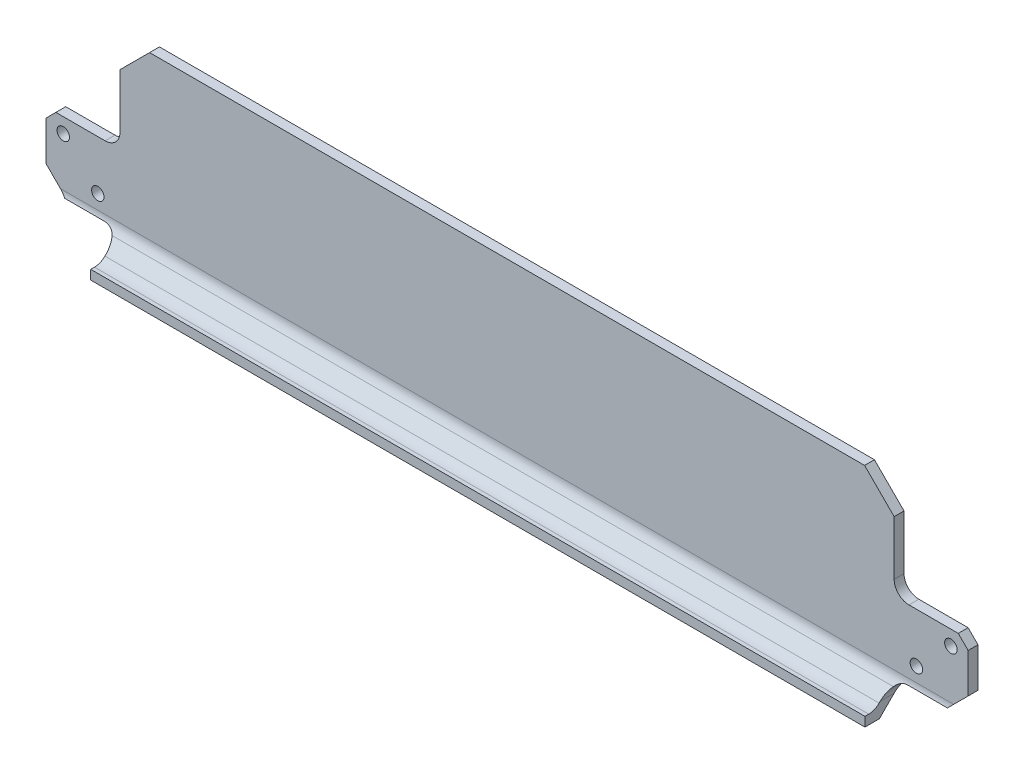
SolidWorks part; units mm, degrees
material "PLA"
ref_plane "Front Plane" through (0, 0, 0) normal (0, 0, 1) x (1, 0, 0)
ref_plane "Top Plane" through (0, 0, 0) normal (0, 1, 0) x (1, 0, 0)
ref_plane "Right Plane" through (0, 0, 0) normal (1, 0, 0) x (0, 0, -1)
sketch "Profile-Sketch" plane through (0, 0, 0) normal (0, 0, 1) x (1, 0, 0)
  line L0 (0, 0) -> (26895.2177, 0) construction
  line L1 (0, 0) -> (0, 26895.2177) construction
  line L2 (-114.3, 12.7) -> (-105.41, 12.7) construction
  line L3 (-114.3, 12.7) -> (-114.3, 21.59) construction
  circle A0 centre (-114.3, 12.7) radius 4 construction
  circle A1 centre (-105.41, 12.7) radius 1.6002 construction
  circle A2 centre (-114.3, 21.59) radius 1.6002 construction
  dimension "D3" = 8
  dimension "D4" = 3.2004
  dimension "D5" = 3.2004
  dimension "D1" = 12.7
  dimension "D2" = 114.3
  dimension "D6" = 8.89
  dimension "D7" = 8.89
sketch "Sketch2" plane through (0, 0, 0) normal (1, 0, 0) x (0, 0, -1)
  line L0 (0, 0) -> (50000, 0) construction
  line L1 (-10.0691, 0) -> (-6.35, 0)
  line L2 (-6.35, 0) -> (0, 6.35)
  line L3 (0, -200000) -> (0, 226895.2177) construction
  line L4 (0, 6.35) -> (0, 50.8)
  line L5 (0, 16.7) -> (0, 8.7) construction
  line L6 (0, 50.8) -> (-2.54, 50.8)
  line L7 (-2.54, 50.8) -> (-2.54, 7.4021)
  line L8 (-2.54, 7.4021) -> (-7.5291, 2.413)
  line L9 (-7.5291, 2.413) -> (-10.0691, 2.413)
  line L10 (-10.0691, 2.413) -> (-10.0691, 0)
  dimension "D1" = 2.54
  dimension "D2" = 50.8
  dimension "D3" = 2.54
  dimension "D4" = 2.413
  dimension "D5" = 45
  dimension "D6" = 2.54
  dimension "D7" = 6.35
extrude "Boss-Extrude1" add sketch "Sketch2" along normal mid plane 199.39
sketch "Sketch3" plane through (0, 0, 0) normal (0, 0, 1) x (1, 0, 0)
  line L0 (-99.695, 25.4) -> (-118.745, 25.4)
  line L1 (-99.695, 50.8) -> (-99.695, 7.4021) construction
  line L2 (-118.745, 25.4) -> (-118.745, 7.62)
  line L3 (-118.745, 7.62) -> (-99.695, 7.62)
  line L4 (-200000, 0) -> (226895.2177, 0) construction
  line L5 (-99.695, 25.4) -> (-99.695, 7.62)
  circle A0 centre (-114.3, 21.59) radius 1.6002 construction
  circle A1 centre (-105.41, 12.7) radius 1.6002 construction
  circle A2 centre (-114.3, 21.59) radius 1.6002
  circle A3 centre (-105.41, 12.7) radius 1.6002
  dimension "D1" = 7.62
  dimension "D2" = 25.4
  dimension "D3" = 19.05
extrude "Mounting-Plate" add sketch "Sketch3" along normal up to surface (2.54 mm away) up to face at (0, 29.1011, 2.54)
mirror "Mirror1" about plane through (0, 0, 0) normal (1, 0, 0) of "Mounting-Plate"
chamfer "Chamfer1" distance 5.08 angle 45 2 edges at (118.745, 7.62, 1.27) (-118.745, 7.62, 1.27)
chamfer "Chamfer2" distance 2.54 angle 45 2 edges at (118.745, 25.4, 1.27) (-118.745, 25.4, 1.27)
chamfer "Chamfer3" distance 7.62 angle 45 2 edges at (99.695, 50.8, 1.27) (-99.695, 50.8, 1.27)
fillet "Fillet1" radius 3.81 6 edges at (0, 2.413, 7.5291) (0, 7.4021, 2.54) (99.695, 7.62, 1.27) (99.695, 25.4, 1.27) (-99.695, 7.62, 1.27) (-99.695, 25.4, 1.27)
equation "\"D5@Profile-Sketch\"=\"D4@Profile-Sketch\""
equation "\"D6@Profile-Sketch\"=\"D7@Profile-Sketch\""
